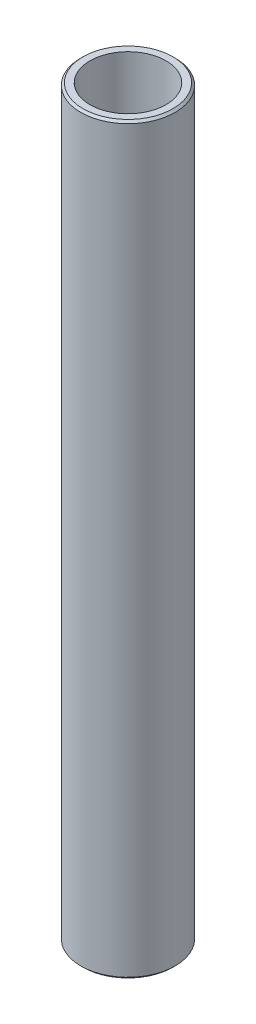
SolidWorks part; units mm, degrees
ref_plane "Front Plane" through (0, 0, 0) normal (0, 0, 1) x (1, 0, 0)
ref_plane "Top Plane" through (0, 0, 0) normal (0, 1, 0) x (1, 0, 0)
ref_plane "Right Plane" through (0, 0, 0) normal (1, 0, 0) x (0, 0, -1)
sketch "Sketch1" plane through (0, 0, 0) normal (0, 1, 0) x (1, 0, 0)
  circle A0 centre (0, 0) radius 35
  dimension "SHAFT_OD" = 70
extrude "Boss-Extrude1" add sketch "Sketch1" along normal blind 551.972
sketch "Sketch2" plane through (0, 0, 0) normal (0, 1, 0) x (1, 0, 0)
  circle A0 centre (0, 0) radius 28.2451
  dimension "BORE_D" = 56.4901
extrude "Cut-Extrude1" cut sketch "Sketch2" along normal through all
chamfer "Chamfer1" distance 1.6056 angle 45 2 edges at (0, 551.972, 35) (0, 0, 35)
